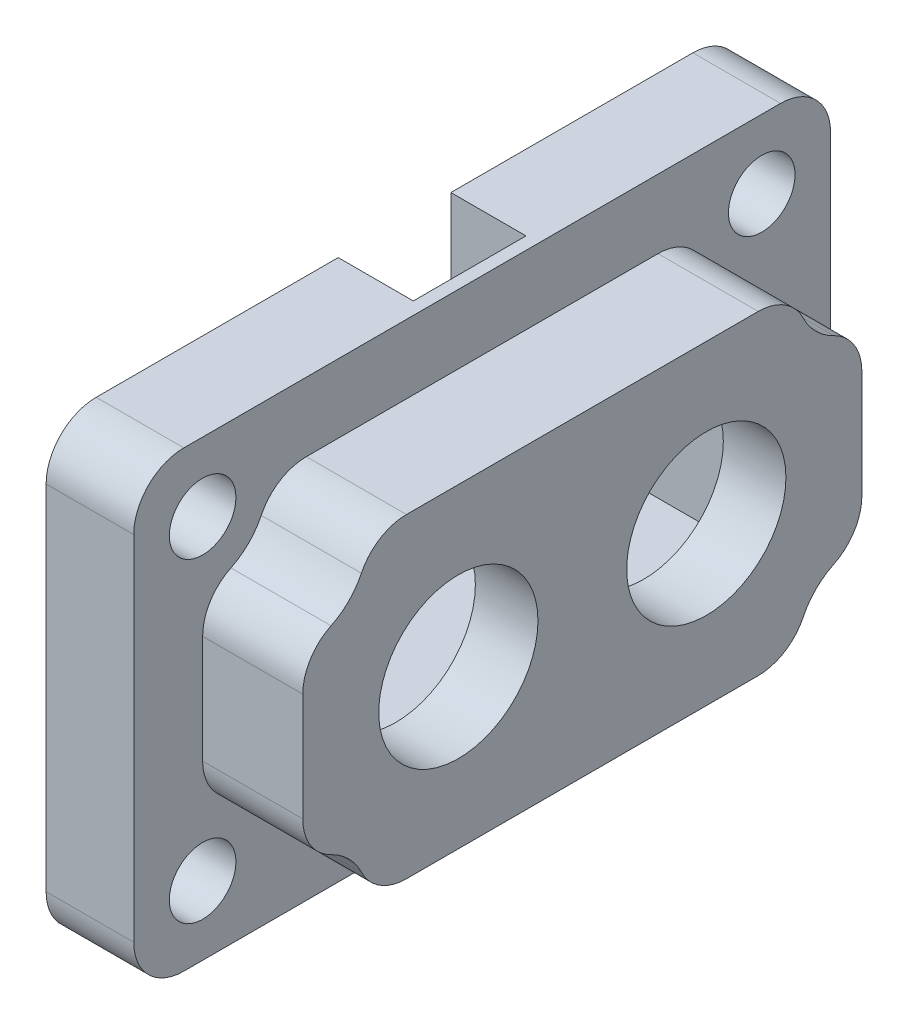
SolidWorks part; units mm, degrees
material "6061-T6 (SS)"
ref_plane "Front Plane" through (0, 0, 0) normal (0, 0, 1) x (1, 0, 0)
ref_plane "Top Plane" through (0, 0, 0) normal (0, 1, 0) x (1, 0, 0)
ref_plane "Right Plane" through (0, 0, 0) normal (1, 0, 0) x (0, 0, -1)
sketch "Sketch1" plane through (0, 0, 0) normal (1, 0, 0) x (0, 0, -1)
  line L0 (0, 10.287) -> (45.2882, 10.287) construction
  line L5 (0, 0) -> (45.2882, 0) construction
  line L6 (0, 0) -> (0, 20.574) construction
  line L7 (0, 20.574) -> (45.2882, 20.574) construction
  line L8 (45.2882, 0) -> (45.2882, 20.574) construction
  line L9 (22.6441, 20.574) -> (22.6441, 0) construction
  line L10 (-12.7, -12.7) -> (57.9882, -12.7)
  line L11 (57.9882, -12.7) -> (57.9882, 33.274)
  line L12 (-12.7, 33.274) -> (57.9882, 33.274)
  line L13 (-12.7, -12.7) -> (-12.7, 33.274)
  circle A0 centre (35.2213, 10.287) radius 8.0772
  circle A1 centre (10.0669, 10.287) radius 8.0772
  dimension "D3" = 9
  dimension "D4" = 16.1544
  dimension "D1" = 45.2882
  dimension "D2" = 20.574
  dimension "D5" = 12.7
extrude "Boss-Extrude1" add sketch "Sketch1" along normal blind 6.35
sketch "Sketch2" plane through (0, 0, 0) normal (-1, 0, 0) x (0, 0, 1)
  line L0 (-45.3644, 20.6502) -> (0.0762, 20.6502)
  line L1 (-57.9882, 33.274) -> (12.7, 33.274)
  line L2 (-57.9882, 33.274) -> (-57.9882, -12.7)
  line L3 (-57.9882, -12.7) -> (12.7, -12.7)
  line L4 (12.7, 33.274) -> (12.7, -12.7)
  line L9 (0.0762, 20.6502) -> (0.0762, -0.0762)
  line L10 (-45.3644, -0.0762) -> (0.0762, -0.0762)
  line L11 (-45.3644, 20.6502) -> (-45.3644, -0.0762)
  dimension "D1" = 45.4406
extrude "Boss-Extrude2" add sketch "Sketch2" along normal blind 12.7
sketch "Sketch3" plane through (0, 33.274, 0) normal (0, 1, 0) x (1, 0, 0)
  line L5 (-12.7, 16.9291) -> (-5.08, 16.9291)
  line L6 (-12.7, 16.9291) -> (-12.7, 28.3591)
  line L7 (-12.7, 28.3591) -> (-5.08, 28.3591)
  line L8 (-5.08, 16.9291) -> (-5.08, 28.3591)
  line L9 (-12.7, 16.9291) -> (-5.08, 28.3591) construction
  line L10 (-12.7, 28.3591) -> (-5.08, 16.9291) construction
  line L12 (-12.7, 22.6441) -> (6.35, 22.6441) construction
  line L13 (-12.7, -12.7) -> (-12.7, 57.9882) construction
  line L14 (6.35, 57.9882) -> (6.35, -12.7) construction
  point P0 (-8.89, 22.6441)
  point P5 (2.2836, 22.6441)
  point P7 (3.0646, 22.6441)
  point P10 (1.2424, 22.6441)
  point P15 (0, 0)
  point P16 (0, 0)
  point P17 (2.4797, 22.6441)
  point P18 (0, 0)
  point P20 (0, 0)
  point P21 (0, 0)
  point P23 (0, 0)
  point P24 (0, 0)
  point P25 (0, 0)
  point P26 (0, 0)
  point P27 (-12.7, 28.3591)
  point P28 (-5.1807, 16.9291)
  dimension "D1" = 7.62
  dimension "D2" = 11.43
extrude "Cut-Extrude1" cut sketch "Sketch3" against normal up to surface (12.6238 mm away) up to face at (-6.35, 20.6502, -22.6441)
sketch "Sketch4" plane through (6.35, 0, 0) normal (1, 0, 0) x (0, 0, -1)
  line L0 (0, 10.287) -> (45.2882, 10.287) construction
  line L1 (-5.715, -5.715) -> (51.0032, -5.715) construction
  line L2 (-5.715, -5.715) -> (-5.715, 26.289) construction
  line L3 (-5.715, 26.289) -> (51.0032, 26.289) construction
  line L4 (51.0032, -5.715) -> (51.0032, 26.289) construction
  line L5 (-5.715, -5.715) -> (51.0032, 26.289) construction
  line L6 (-5.715, 26.289) -> (51.0032, -5.715) construction
  line L7 (-12.7, -12.7) -> (-12.7, 33.274) construction
  line L8 (-12.7, 33.274) -> (57.9882, 33.274) construction
  line L11 (51.0032, 19.685) -> (51.0032, 0.889)
  line L12 (44.3992, -5.715) -> (0.889, -5.715)
  line L15 (44.3992, 26.289) -> (0.889, 26.289)
  line L16 (-5.715, 19.685) -> (-5.715, 0.889)
  line L18 (-12.7, -12.7) -> (57.9882, -12.7)
  line L19 (-12.7, -12.7) -> (-12.7, 33.274)
  line L20 (-12.7, 33.274) -> (57.9882, 33.274)
  line L21 (57.9882, -12.7) -> (57.9882, 33.274)
  circle A1 centre (-5.715, 26.289) radius 3.3782
  circle A2 centre (-5.715, -5.715) radius 3.3782
  circle A3 centre (51.0032, -5.715) radius 3.3782
  circle A4 centre (51.0032, 26.289) radius 3.3782
  circle A5 centre (-5.715, 26.289) radius 5.588 construction
  arc A6 (44.3992, 26.289) -> (51.0032, 19.685) centre (51.0032, 26.289) ccw
  arc A7 (51.0032, 0.889) -> (44.3992, -5.715) centre (51.0032, -5.715) ccw
  arc A8 (0.889, -5.715) -> (-5.715, 0.889) centre (-5.715, -5.715) ccw
  arc A9 (-5.715, 19.685) -> (0.889, 26.289) centre (-5.715, 26.289) ccw
  point P0 (22.6441, 10.287)
  line M5 (-12.7, 33.274) -> (-12.7, -12.7)
  line M6 (-12.7, -12.7) -> (57.9882, -12.7)
  line M7 (57.9882, -12.7) -> (57.9882, 33.274)
  line M8 (57.9882, 33.274) -> (-12.7, 33.274)
  dimension "D1" = 6.7564
  dimension "D2" = 11.176
  dimension "D5" = 6.604
  dimension "D3" = 6.985
  dimension "D4" = 6.985
extrude "Cut-Extrude2" cut sketch "Sketch4" against normal blind 10.16 contours A1 A2 A3 A4 L16 A9 L15 A6 L11 A7 L12 A8 M8 M5 M6 M7 | A2 | A1 | A4 | A3 region at (6.35, 10.287, 11.8568) region at (6.35, 26.289, 5.715) region at (6.35, -5.715, 5.715) region at (6.35, -5.715, -51.0032) region at (6.35, 26.289, -51.0032)
extrude "Cut-Extrude3" cut sketch "Sketch4<3>" against normal through all contours A2 | A1 | A4 | A3 region at (6.35, 26.289, 5.715) region at (6.35, -5.715, 5.715) region at (6.35, -5.715, -51.0032) region at (6.35, 26.289, -51.0032)
sketch "Sketch4<3>" plane through (6.35, 0, 0) normal (1, 0, 0) x (0, 0, -1) same geometry as "Sketch4"
fillet "Fillet1" radius 5.08 12 edges at (-8.255, 33.274, -57.9882) (-8.255, -12.7, -57.9882) (-8.255, -12.7, 12.7) (-8.255, 33.274, 12.7) (1.27, 0.889, 5.715) (1.27, -5.715, -0.889) (1.27, -5.715, -44.3992) (1.27, 0.889, -51.0032) (1.27, 19.685, -51.0032) (1.27, 26.289, -44.3992) (1.27, 19.685, 5.715) (1.27, 26.289, -0.889)
equation "\"D4@Sketch4\"=\"D3@Sketch4\""
